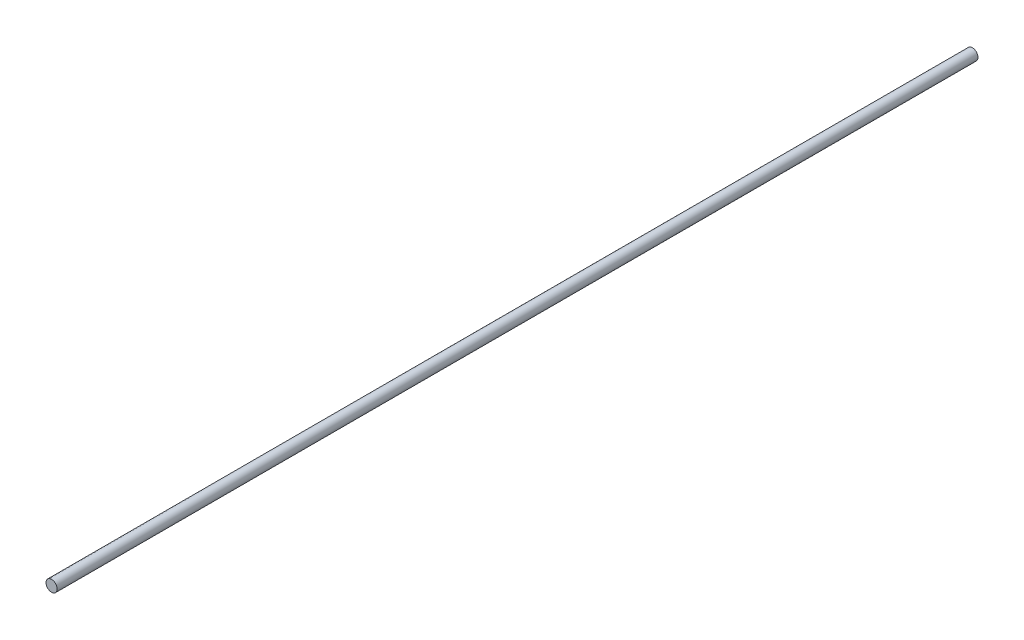
SolidWorks part; units mm, degrees
material "Plain Carbon Steel"
ref_plane "Front Plane" through (0, 0, 0) normal (0, 0, 1) x (1, 0, 0)
ref_plane "Top Plane" through (0, 0, 0) normal (0, 1, 0) x (1, 0, 0)
ref_plane "Right Plane" through (0, 0, 0) normal (1, 0, 0) x (0, 0, -1)
sketch "Sketch1" plane through (0, 0, 0) normal (0, 0, 1) x (1, 0, 0)
  circle A0 centre (0, 0) radius 4.7625
  dimension "D1" = 9.525
extrude "Boss-Extrude1" add sketch "Sketch1" against normal blind 784.225
ref_plane "Plane1" [suppressed] through (0, 0, -1.27) normal (0, 0, 1) x (1, 0, 0)
sketch "Sketch2" [suppressed] plane through (0, 0, -1.27) normal (0, 0, 1) x (1, 0, 0)
  circle A0 centre (0, 0) radius 4.7625 construction
  circle A1 centre (0, 0) radius 4.7625
curve "Helix/Spiral1" [suppressed] pitch 2.54 height 50.8 turns 20
ref_plane "Plane2" [suppressed] through (-4.7625, 0, -1.27) normal (0, 0.9964, -0.0846) x (1, 0, 0)
sketch "Sketch4" [suppressed] plane through (-4.7625, 0, -1.27) normal (0, 0.9964, -0.0846) x (1, 0, 0)
  line L0 (0, 0) -> (-1.7907, 0) construction
  line L1 (0, 656.7682) -> (0, -1.2654) construction
  line L2 (-1.7907, 0.4322) -> (-1.7907, -0.4322)
  line L3 (-1.7907, -0.4322) -> (1.2799, -1.2264)
  line L4 (1.2799, -1.2264) -> (1.2799, 1.2264)
  line L5 (-1.7907, 0.4322) -> (1.2799, 1.2264)
  line L6 (0, 0.8953) -> (0, -0.8953) construction
  point P8 (1.2799, 0)
  point P10 (0, 0.8953)
  point P11 (0, -0.8953)
  dimension "D1" = 1.7907
  dimension "D2" = 14.5
  dimension "D3" = 1.7907
sweep "ACME 1/2 - 10 Thread" [suppressed] add profiles "Sketch4" path "Helix/Spiral1"
sketch "Sketch5" [suppressed] plane through (0, 0.107, -0.0091) normal (0, -0.9964, 0.0846) x (1, 0, 0)
  line L4 (-6.5532, -0.8332) -> (-6.5532, -1.6977)
  line L5 (-3.4826, -0.0391) -> (-6.5532, -0.8332)
  line L6 (-3.4826, -2.4918) -> (-3.4826, -0.0391)
  line L7 (-6.5532, -1.6977) -> (-3.4826, -2.4918)
  line L8 (-6.5532, -0.8332) -> (-6.5532, -1.6977)
  line L9 (-3.4826, -0.0391) -> (-6.5532, -0.8332)
  line L10 (-3.4826, -2.4918) -> (-3.4826, -0.0391)
  line L11 (-6.5532, -1.6977) -> (-3.4826, -2.4918)
  dimension "D1" = 0
revolve "Revolve1" [suppressed] add sketch "Sketch5" angle 360 about L10
ref_plane "Plane3" [suppressed] through (0, 0, -50.8) normal (0, 0, 1) x (1, 0, 0)
sketch "Sketch8" [suppressed] plane through (0, 0, -50.8) normal (0, 0, 1) x (1, 0, 0)
  circle A0 centre (0, 0) radius 4.7625
  dimension "D1" = 9.525
extrude "Boss-Extrude2" [suppressed] add sketch "Sketch8" against normal up to surface (609.6 mm away)
ref_plane "Plane4" [suppressed] through (0, 3.81, 0) normal (0, 1, 0) x (1, 0, 0)
sketch "Sketch9" [suppressed] plane through (0, 3.81, 0) normal (0, 1, 0) x (1, 0, 0)
  line L1 (-12.7, 0) -> (12.7, 0)
  line L2 (-12.7, 0) -> (-12.7, 12.7)
  line L3 (-12.7, 12.7) -> (12.7, 12.7)
  line L4 (12.7, 0) -> (12.7, 12.7)
  dimension "D1" = 12.7
  dimension "D2" = 25.4
extrude "Cut-Extrude3" [suppressed] cut sketch "Sketch9" along normal blind 1524
